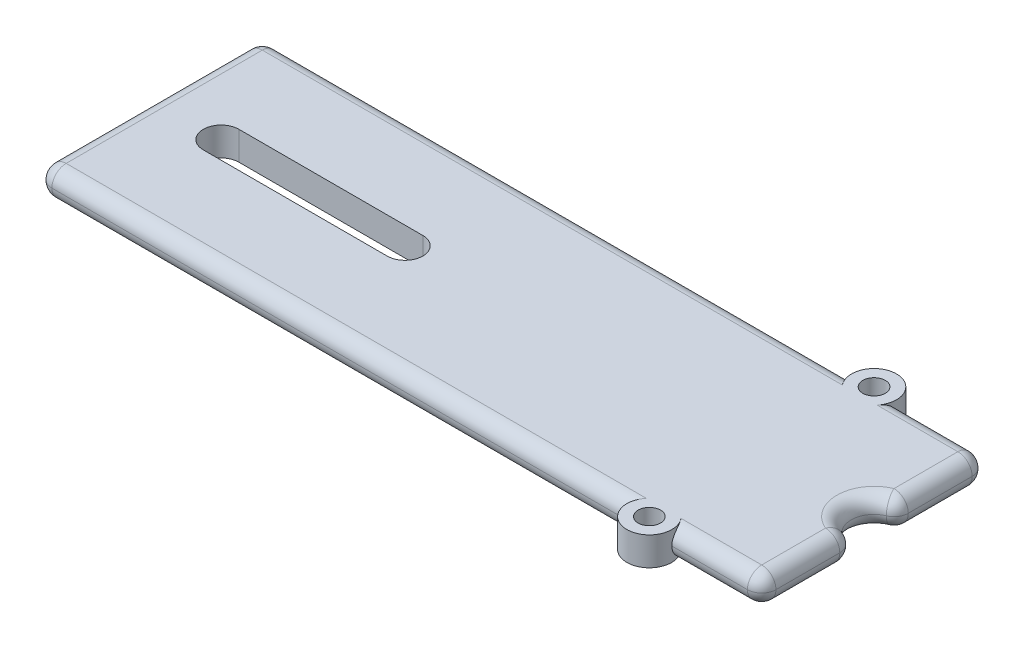
SolidWorks part; units mm, degrees
ref_plane "Plan de face" through (0, 0, 0) normal (0, 0, 1) x (1, 0, 0)
ref_plane "Plan de dessus" through (0, 0, 0) normal (0, 1, 0) x (1, 0, 0)
ref_plane "Plan de droite" through (0, 0, 0) normal (1, 0, 0) x (0, 0, -1)
sketch "Esquisse1" plane through (0, 0, 0) normal (0, 1, 0) x (1, 0, 0)
  line L0 (10, 0) -> (10, 20) construction
  line L1 (0, 0) -> (20, 0)
  line L2 (0, 0) -> (0, 20)
  line L3 (0, 20) -> (20, 20)
  line L4 (20, 0) -> (20, 20)
  line L5 (0, 10) -> (20, 10) construction
  line L6 (10, 10) -> (-21.75, 10) construction
  line L7 (0, 0) -> (-44.45, 0)
  line L8 (0, 0) -> (0, 20)
  line L9 (0, 20) -> (-44.45, 20)
  line L10 (-44.45, 0) -> (-44.45, 20)
  line L11 (-21.75, 10) -> (-38.1178, 10) construction
  line L12 (-21.75, 8.4125) -> (-38.1178, 8.4125)
  line L13 (-21.75, 11.5875) -> (-38.1178, 11.5875)
  circle A0 centre (10, 20) radius 2
  circle A1 centre (10, 20) radius 1
  circle A2 centre (10, 0) radius 1
  circle A3 centre (10, 0) radius 2
  arc A4 (-21.75, 8.4125) -> (-21.75, 11.5875) centre (-21.75, 10) ccw
  arc A5 (-38.1178, 11.5875) -> (-38.1178, 8.4125) centre (-38.1178, 10) ccw
  circle A6 centre (20, 10) radius 2.032
  point P17 (-29.9339, 10)
  dimension "D3" = 4
  dimension "D4" = 2
  dimension "D7" = 1.5875
  dimension "D8" = 4.064
  dimension "D1" = 20
  dimension "D2" = 10
  dimension "D5" = 44.45
  dimension "D6" = 31.75
extrude "Boss.-Extru.1" add sketch "Esquisse1" along normal blind 2.54 contours L9 L10 L7 L1 L4 L3 | L12 A5 L13 A4
extrude "Boss.-Extru.2" add sketch "Esquisse1<3>" along normal blind 2.54 contours A3 | A2 | A0 | A1
sketch "Esquisse1<3>" plane through (0, 0, 0) normal (0, 1, 0) x (1, 0, 0) same geometry as "Esquisse1"
extrude "Enlèv. mat.-Extru.1" cut sketch "Esquisse1<4>" along normal blind 7.62 contours A1 | A2 | A6
sketch "Esquisse1<4>" plane through (0, 0, 0) normal (0, 1, 0) x (1, 0, 0) same geometry as "Esquisse1"
fillet "Congé1" radius 1.27 6 edges at (20, 1.27, -12.032) (20, 1.27, -7.968) (20, 1.27, 0) (20, 1.27, -20) (-44.45, 1.27, -20) (-44.45, 1.27, 0)
fillet "Congé2" radius 1.27 10 edges at (-17.59, 2.54, -20) (-44.078, 2.54, -19.628) (-44.45, 2.54, -10) (-44.078, 2.54, -0.372) (-17.59, 0, -20) (-44.078, 0, -19.628) (-44.45, 0, -10) (-44.078, 0, -0.372) (-17.59, 2.54, 0) (-17.59, 0, 0)
fillet "Congé3" radius 1.27 18 edges at (15.365, 2.54, 0) (19.628, 2.54, -0.372) (20, 2.54, -4.111) (19.7867, 2.54, -7.6565) (17.968, 2.54, -10) (19.7867, 2.54, -12.3435) (20, 2.54, -15.889) (19.628, 2.54, -19.628) (15.365, 0, -20) (19.628, 0, -19.628) (20, 0, -15.889) (19.7867, 0, -12.3435) (17.968, 0, -10) (19.7867, 0, -7.6565) (20, 0, -4.111) (19.628, 0, -0.372) (15.365, 2.54, -20) (15.365, 0, 0)
